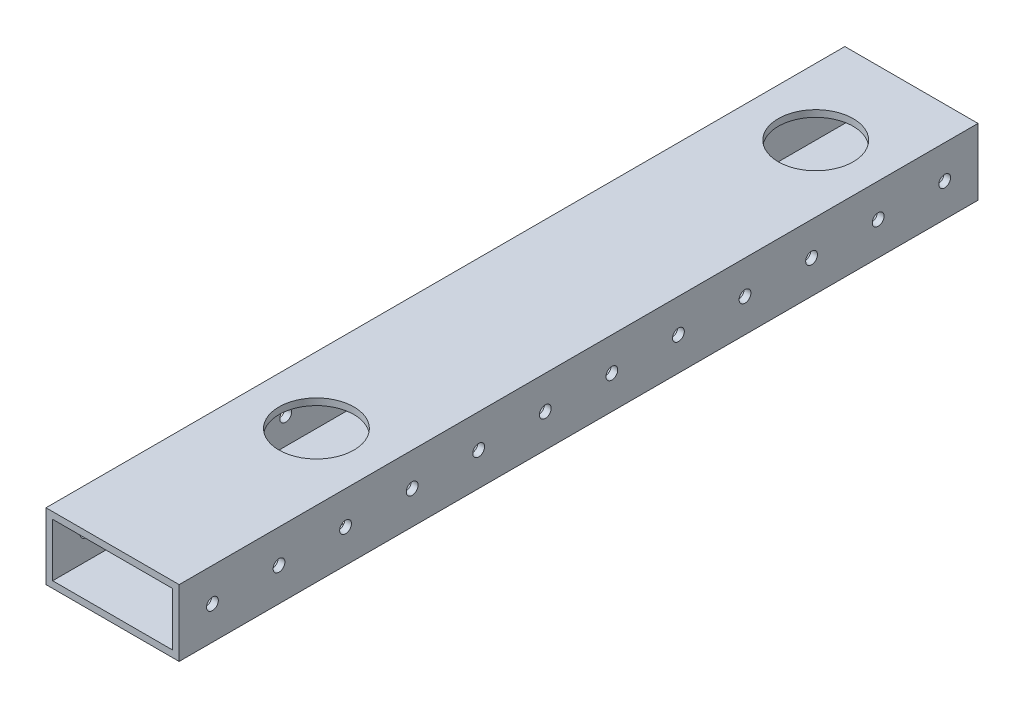
SolidWorks part; units mm, degrees
ref_plane "Front Plane" through (0, 0, 0) normal (0, 0, 1) x (1, 0, 0)
ref_plane "Top Plane" through (0, 0, 0) normal (0, 1, 0) x (1, 0, 0)
ref_plane "Right Plane" through (0, 0, 0) normal (1, 0, 0) x (0, 0, -1)
sketch "Sketch1" plane through (0, 0, 0) normal (0, 0, 1) x (1, 0, 0)
  line L1 (-25.4, -12.7) -> (25.4, -12.7)
  line L2 (-25.4, -12.7) -> (-25.4, 12.7)
  line L3 (-25.4, 12.7) -> (25.4, 12.7)
  line L4 (25.4, -12.7) -> (25.4, 12.7)
  line L5 (-25.4, -12.7) -> (25.4, 12.7) construction
  line L6 (-25.4, 12.7) -> (25.4, -12.7) construction
  line L7 (-22.86, -10.16) -> (22.86, -10.16)
  line L8 (-22.86, -10.16) -> (-22.86, 10.16)
  line L9 (-22.86, 10.16) -> (22.86, 10.16)
  line L10 (22.86, -10.16) -> (22.86, 10.16)
  line L11 (-22.86, -10.16) -> (22.86, 10.16) construction
  line L12 (-22.86, 10.16) -> (22.86, -10.16) construction
  point P0 (0, 0)
  point P6 (0, 0)
  dimension "D1" = 50.8
  dimension "D2" = 25.4
  dimension "D3" = 2.54
  dimension "D4" = 2.54
extrude "Boss-Extrude1" add sketch "Sketch1" against normal blind 533.4
hole_wizard "#8 Clearance Hole1" positions "Sketch2" profile "Sketch3" hole size "#8" standard "ANSI Inch" end condition through all
sketch "Sketch2" plane through (25.4, 0, 0) normal (1, 0, 0) x (0, 0, -1)
  line L0 (533.4, -12.7) -> (0, -12.7) construction
  point P0 (12.7, 0)
  point P16 (38.1, 0)
  point P17 (63.5, 0)
  point P18 (88.9, 0)
  point P19 (114.3, 0)
  point P20 (139.7, 0)
  point P21 (165.1, 0)
  point P22 (190.5, 0)
  point P23 (215.9, 0)
  point P24 (241.3, 0)
  point P25 (266.7, 0)
  point P26 (292.1, 0)
  point P27 (317.5, 0)
  point P28 (342.9, 0)
  point P29 (368.3, 0)
  point P30 (393.7, 0)
  point P31 (419.1, 0)
  point P32 (444.5, 0)
  point P33 (469.9, 0)
  point P34 (495.3, 0)
  point P35 (520.7, 0)
  dimension "D1" = 12.7
  dimension "D2" = 12.7
  dimension "D3" = 21
sketch "Sketch3" plane through (25.4, 0, -12.7) normal (0, 1, 0) x (0, 0, -1)
  line L0 (0, 0) -> (0, 50.8)
  line L1 (0, 50.8) -> (2.2479, 50.8)
  line L2 (2.2479, 50.8) -> (2.2479, 0)
  line L5 (2.2479, 0) -> (0, 0)
  line L11 (0, -6.35) -> (0, 107.95) construction
  dimension "Thru Hole Dia." = 4.4958
  dimension "Thru Hole Depth" = 50.8
sketch "Sketch4" plane through (0, 12.7, 0) normal (0, 1, 0) x (1, 0, 0)
  line L0 (-7.2063, 228.6) -> (135.5131, 228.6)
  line L3 (135.5131, 228.6) -> (135.5131, -17.6414)
  line L4 (135.5131, -17.6414) -> (-94.0569, -17.6414)
  line L5 (-94.0569, -17.6414) -> (-94.0569, 228.6)
  line L6 (-94.0569, 228.6) -> (-7.2063, 228.6)
extrude "Cut-Extrude2" cut sketch "Sketch4" against normal blind 76.962
ref_plane "Plane1" through (-25.4, 12.7, -533.4) normal (0, 0, 1) x (1, 0, 0)
sketch "Sketch5" plane through (0, 12.7, 0) normal (0, 1, 0) x (1, 0, 0)
  circle A0 centre (0, 496.8875) radius 14.2875
  circle A1 centre (0, 306.3875) radius 14.2875
  point P9 (0, 495.6911)
  point P11 (2.4944, 363.1259)
  point P12 (0.6101, 300.005)
  dimension "D2" = 28.575
  dimension "D1" = 190.5
extrude "Cut-Extrude3" cut sketch "Sketch5" against normal blind 452.12
